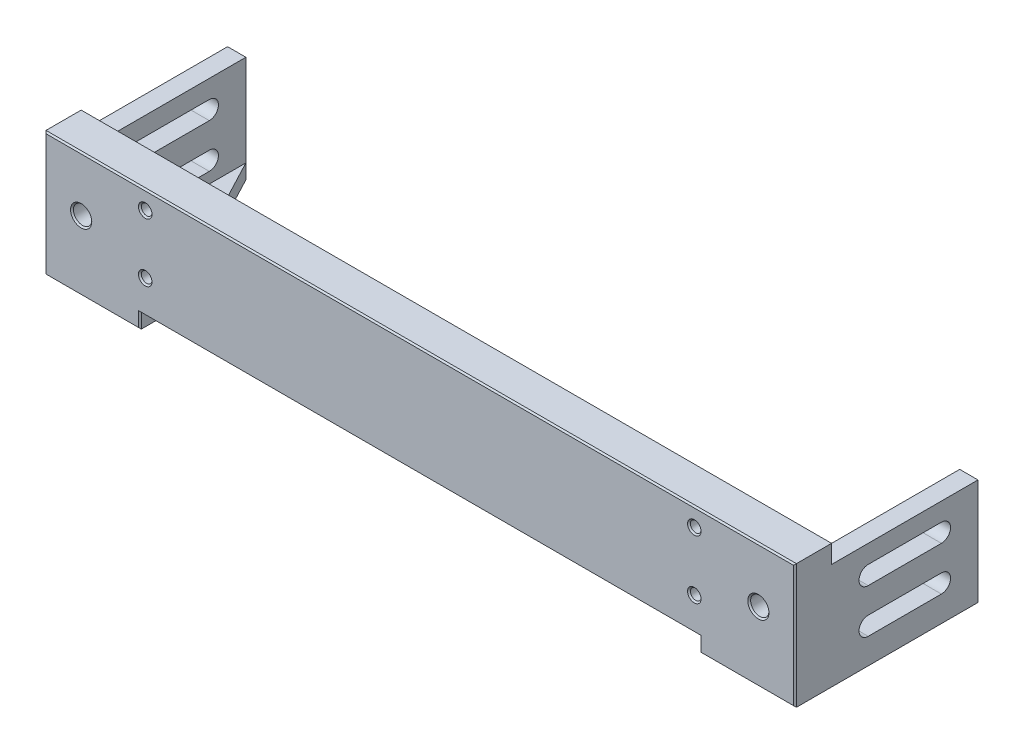
SolidWorks part; units mm, degrees
ref_plane "Front Plane" through (0, 0, 0) normal (0, 0, 1) x (1, 0, 0)
ref_plane "Top Plane" through (0, 0, 0) normal (0, 1, 0) x (1, 0, 0)
ref_plane "Right Plane" through (0, 0, 0) normal (1, 0, 0) x (0, 0, -1)
sketch "Sketch1" plane through (0, 0, 0) normal (0, 0, 1) x (1, 0, 0)
  line L0 (0, 0) -> (0, 19.05) construction
  line L1 (-130.175, 19.05) -> (130.175, 19.05)
  line L2 (-130.175, 19.05) -> (-130.175, -19.05)
  line L3 (-130.175, -19.05) -> (130.175, -19.05)
  line L4 (130.175, 19.05) -> (130.175, -19.05)
  line L5 (-130.175, 19.05) -> (130.175, -19.05) construction
  line L6 (-130.175, -19.05) -> (130.175, 19.05) construction
  line L7 (-81.28, 10.16) -> (-81.28, -10.16) construction
  line L8 (-81.28, 0) -> (-117.475, 0) construction
  circle A0 centre (-117.475, 0) radius 3.175
  circle A1 centre (117.475, 0) radius 3.175
  circle A7 centre (-95.25, 12.7) radius 1.85
  circle A8 centre (-95.25, -7.62) radius 1.85
  circle A9 centre (95.25, -7.62) radius 1.85
  circle A10 centre (95.25, 12.7) radius 1.85
  point P0 (0, 0)
  dimension "D1" = 6.35
  dimension "D6" = 20.32
  dimension "D9" = 3.7
  dimension "D10" = 190.5
  dimension "D2" = 260.35
  dimension "D3" = 12.7
  dimension "D4" = 38.1
  dimension "D5" = 20.32
  dimension "D7" = 81.28
  dimension "D8" = 12.7
extrude "Boss-Extrude1" add sketch "Sketch1" along normal blind 12.7
sketch "Sketch2" plane through (0, 0, 0) normal (0, 0, -1) x (-1, 0, 0)
  line L0 (-130.175, 12.7) -> (-130.175, -19.05)
  line L1 (-130.175, -19.05) -> (-123.825, -19.05)
  line L2 (130.175, -19.05) -> (-130.175, -19.05) construction
  line L3 (-123.825, -19.05) -> (-123.825, 12.7)
  line L5 (-123.825, 12.7) -> (-130.175, 12.7)
  dimension "D1" = 6.35
  dimension "D2" = 31.75
extrude "Boss-Extrude2" add sketch "Sketch2" along normal blind 50.8
sketch "Sketch3" plane through (123.825, 0, 0) normal (-1, 0, 0) x (0, 0, 1)
  line L0 (-38.1, 6.35) -> (-12.7, 6.35)
  line L1 (-25.4, 12.7) -> (-25.4, 6.35) construction
  line L2 (-38.1, 0) -> (-12.7, 0)
  line L3 (-50.8, 12.7) -> (0, 12.7) construction
  line L4 (-38.1, -8.89) -> (-12.7, -8.89)
  line L5 (-25.4, 6.35) -> (-25.4, -8.89) construction
  line L6 (-38.1, -15.24) -> (-12.7, -15.24)
  line L8 (12.7, -19.05) -> (-50.8, -19.05) construction
  arc A0 (-38.1, 6.35) -> (-38.1, 0) centre (-38.1, 3.175) ccw
  arc A1 (-38.1, -8.89) -> (-38.1, -15.24) centre (-38.1, -12.065) ccw
  arc A2 (-12.7, -15.24) -> (-12.7, -8.89) centre (-12.7, -12.065) ccw
  arc A3 (-12.7, 0) -> (-12.7, 6.35) centre (-12.7, 3.175) ccw
  dimension "D1" = 8.89
  dimension "D4" = 25.4
  dimension "D2" = 25.4
  dimension "D3" = 6.35
  dimension "D5" = 6.35
extrude "Cut-Extrude1" cut sketch "Sketch3" against normal blind 50.8
sketch "Sketch4" plane through (0, -19.05, 0) normal (0, -1, 0) x (-1, 0, 0)
  line L0 (-123.825, 50.8) -> (-97.1, 0)
  line L1 (-123.825, 50.8) -> (-130.175, 50.8)
  line L2 (-130.175, 50.8) -> (-130.175, -12.7)
  line L3 (-130.175, -12.7) -> (-97.1, -12.7)
  line L4 (130.175, -12.7) -> (-130.175, -12.7) construction
  line L5 (-97.1, -12.7) -> (-97.1, 0)
extrude "Boss-Extrude3" add sketch "Sketch4" along normal blind 5.08
mirror "Mirror1" about plane through (0, 0, 0) normal (1, 0, 0) of "Boss-Extrude1", "Boss-Extrude2", "Boss-Extrude3", "Cut-Extrude1"
chamfer "Chamfer1" distance 0.5 angle 45 14 edges at (93.4, 12.7, 12.7) (-93.4, 12.7, 12.7) (114.3, 0, 12.7) (-114.3, 0, 12.7) (-97.1, -7.62, 12.7) (97.1, -7.62, 12.7) (113.6375, -24.13, 12.7) (97.1, -21.59, 12.7) (0, -19.05, 12.7) (-97.1, -21.59, 12.7) (-113.6375, -24.13, 12.7) (-130.175, -2.54, 12.7) (0, 19.05, 12.7) (130.175, -2.54, 12.7)
